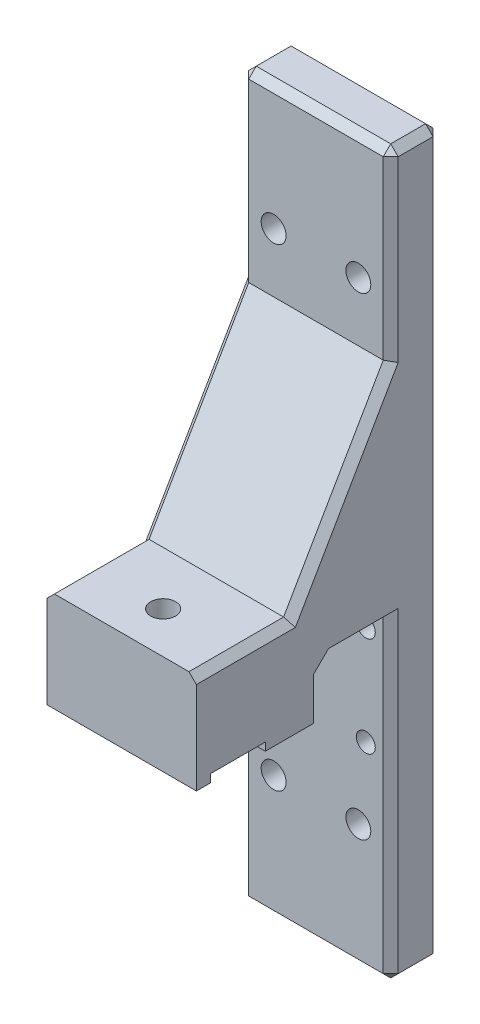
SolidWorks part; units mm, degrees
ref_plane "Front Plane" through (0, 0, 0) normal (0, 0, 1) x (1, 0, 0)
ref_plane "Top Plane" through (0, 0, 0) normal (0, 1, 0) x (1, 0, 0)
ref_plane "Right Plane" through (0, 0, 0) normal (1, 0, 0) x (0, 0, -1)
sketch "Sketch1" plane through (0, 0, 0) normal (0, 0, 1) x (1, 0, 0)
  line L1 (0, 0) -> (30, 0)
  line L2 (0, 0) -> (0, 145)
  line L3 (0, 145) -> (30, 145)
  line L4 (30, 0) -> (30, 145)
  dimension "D1" = 30
  dimension "D2" = 145
extrude "Boss-Extrude1" add sketch "Sketch1" along normal blind 10
sketch "Sketch2" plane through (0, 0, 10) normal (0, 0, 1) x (1, 0, 0)
  line L0 (30, 0) -> (30, 145) construction
  line L1 (6.5, 120) -> (23.5, 120)
  line L2 (6.5, 120) -> (6.5, 25)
  line L3 (6.5, 25) -> (23.5, 25)
  line L4 (23.5, 120) -> (23.5, 25)
  line L5 (6.5, 120) -> (23.5, 25) construction
  line L6 (6.5, 25) -> (23.5, 120) construction
  line L7 (30, 145) -> (0, 145) construction
  circle A0 centre (23.5, 120) radius 2.5
  circle A1 centre (6.5, 120) radius 2.5
  circle A2 centre (6.5, 25) radius 2.5
  circle A3 centre (23.5, 25) radius 2.5
  point P0 (15, 72.5)
  point P7 (30, 72.5)
  point P10 (15, 145)
  dimension "D3" = 5
  dimension "D1" = 17
  dimension "D2" = 95
extrude "Cut-Extrude1" cut sketch "Sketch2" against normal blind 32 contours L1 A1 L2 | L2 A1 L1 | L1 A0 L4 | L4 A0 L1 | L3 A3 L4 | L4 A3 L3 | L2 A2 L3 | L3 A2 L2
sketch "Sketch3" plane through (0, 0, 10) normal (0, 0, 1) x (1, 0, 0)
  line L0 (0, 0) -> (30, 0) construction
  line L1 (5, 40) -> (25, 40)
  line L2 (5, 40) -> (5, 60)
  line L3 (5, 60) -> (25, 60)
  line L4 (25, 40) -> (25, 60)
  line L5 (5, 40) -> (25, 60) construction
  line L6 (5, 60) -> (25, 40) construction
  circle A0 centre (25, 60) radius 1.9
  circle A1 centre (5, 60) radius 1.9
  circle A2 centre (5, 40) radius 1.9
  circle A3 centre (25, 40) radius 1.9
  point P0 (15, 50)
  point P7 (15, 0)
  dimension "D2" = 3.8
  dimension "D1" = 20
  dimension "D3" = 40
extrude "Cut-Extrude2" cut sketch "Sketch3" against normal blind 32 contours L3 A1 L2 | L2 A1 L3 | L4 A0 L3 | L3 A0 L4 | L2 A2 L1 | L1 A2 L2 | L1 A3 L4 | L4 A3 L1
sketch "Sketch4" plane through (0, 0, 0) normal (0, 0, -1) x (-1, 0, 0)
  circle A0 centre (-5, 60) radius 3.5
  circle A1 centre (-5, 40) radius 3.5
  circle A2 centre (-25, 40) radius 3.5
  circle A3 centre (-25, 60) radius 3.5
  dimension "D1" = 7
extrude "Cut-Extrude3" cut sketch "Sketch4" against normal blind 5
sketch "Sketch5" plane through (0, 0, 10) normal (0, 0, 1) x (1, 0, 0)
  line L0 (0, 145) -> (0, 0) construction
  line L1 (0, 63.5) -> (30, 63.5)
  line L2 (0, 63.5) -> (0, 73.5)
  line L3 (0, 73.5) -> (30, 73.5)
  line L4 (30, 63.5) -> (30, 73.5)
  line L5 (30, 0) -> (30, 145) construction
  circle A0 centre (25, 60) radius 1.9 construction
  dimension "D2" = 3.5
  dimension "D1" = 10
extrude "Boss-Extrude2" add sketch "Sketch5" along normal blind 39
sketch "Sketch6" plane through (0, 63.5, 0) normal (0, -1, 0) x (1, 0, 0)
  line L0 (30, 49) -> (30, 10) construction
  line L1 (0, 49) -> (30, 49)
  line L2 (0, 49) -> (0, 24)
  line L3 (0, 24) -> (30, 24)
  line L4 (30, 49) -> (30, 24)
  dimension "D1" = 25
extrude "Boss-Extrude3" add sketch "Sketch6" along normal blind 10
sketch "Sketch7" plane through (30, 0, 0) normal (1, 0, 0) x (0, 0, -1)
  line L0 (-24, 53.5) -> (-49, 53.5) construction
  line L1 (-46.1751, 53.5) -> (-35.1751, 53.5)
  line L2 (-46.1751, 53.5) -> (-46.1751, 55.1)
  line L3 (-46.1751, 55.1) -> (-35.1751, 55.1)
  line L4 (-35.1751, 53.5) -> (-35.1751, 55.1)
  dimension "D1" = 11
  dimension "D2" = 1.6
extrude "Cut-Extrude4" cut sketch "Sketch7" against normal blind 61
sketch "Sketch8" plane through (0, 55.1, 0) normal (0, -1, 0) x (1, 0, 0)
  line L0 (30, 35.1751) -> (30, 46.1751) construction
  line L1 (0, 46.1751) -> (30, 46.1751) construction
  circle A0 centre (15, 40.6751) radius 2.5
  point P4 (30, 40.6751)
  point P7 (15, 46.1751)
  dimension "D1" = 5
extrude "Cut-Extrude5" cut sketch "Sketch8" against normal blind 61
chamfer "Chamfer1" distance 20 angle 60 1 edges at (15, 73.5, 10)
chamfer "Chamfer2" distance 1.5 angle 45 24 edges at (30, 0, 5) (15, 0, 0) (30, 72.5, 0) (30, 31.75, 10) (15, 0, 10) (0, 31.75, 10) (0, 0, 5) (0, 72.5, 0) (0, 145, 5) (15, 145, 0) (30, 145, 5) (30, 73.5, 39.5) (30, 90.8205, 20) (30, 126.5705, 10) (15, 145, 10) (0, 126.5705, 10) (0, 90.8205, 20) (0, 73.5, 39.5) (30, 63.5, 17) (0, 63.5, 17) (30, 58.5, 24) (15, 53.5, 24) (0, 58.5, 24) (15, 63.5, 24)
